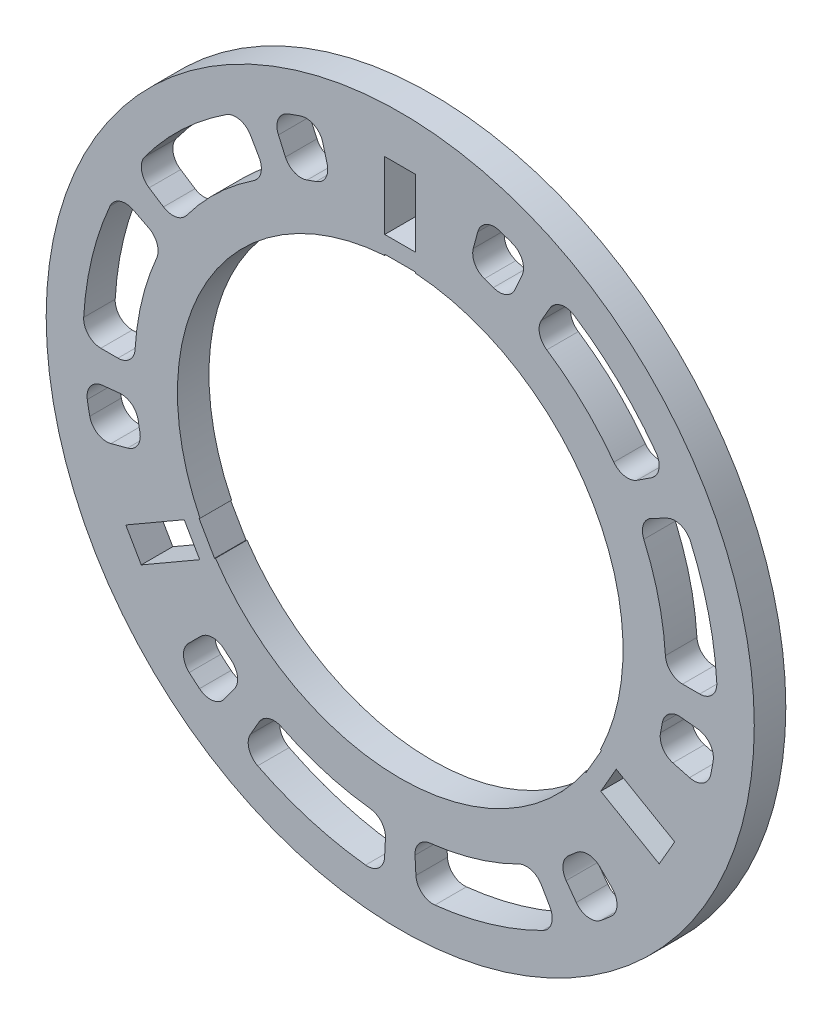
SolidWorks part; units mm, degrees
ref_plane "Front Plane" through (0, 0, 0) normal (0, 0, 1) x (1, 0, 0)
ref_plane "Top Plane" through (0, 0, 0) normal (0, 1, 0) x (1, 0, 0)
ref_plane "Right Plane" through (0, 0, 0) normal (1, 0, 0) x (0, 0, -1)
sketch "Sketch1" plane through (0, 0, 0) normal (0, 0, 1) x (1, 0, 0)
  line L0 (0, 0) -> (0, 50.8) construction
  line L1 (47.9712, -31.0114) -> (50.8422, -26.0386)
  line L2 (2.871, 57.05) -> (-2.871, 57.05)
  line L3 (2.871, 57.05) -> (2.871, 44.55)
  line L4 (2.871, 44.55) -> (-2.871, 44.55)
  line L5 (-2.871, 57.05) -> (-2.871, 44.55)
  line L6 (2.871, 57.05) -> (-2.871, 44.55) construction
  line L7 (2.871, 44.55) -> (-2.871, 57.05) construction
  line L8 (47.9712, -31.0114) -> (37.1459, -24.7614)
  line L9 (37.1459, -24.7614) -> (40.0169, -19.7886)
  line L10 (50.8422, -26.0386) -> (40.0169, -19.7886)
  line L11 (47.9712, -31.0114) -> (40.0169, -19.7886) construction
  line L12 (37.1459, -24.7614) -> (50.8422, -26.0386) construction
  line L13 (-50.8422, -26.0386) -> (-47.9712, -31.0114)
  line L14 (-50.8422, -26.0386) -> (-40.0169, -19.7886)
  line L15 (-40.0169, -19.7886) -> (-37.1459, -24.7614)
  line L16 (-47.9712, -31.0114) -> (-37.1459, -24.7614)
  line L17 (-50.8422, -26.0386) -> (-37.1459, -24.7614) construction
  line L18 (-40.0169, -19.7886) -> (-47.9712, -31.0114) construction
  line L19 (-2.871, 41.375) -> (2.871, 41.375)
  line L20 (-2.871, 41.175) -> (-2.871, 41.375)
  line L21 (2.871, 41.175) -> (2.871, 41.375)
  line L22 (34.2231, -23.0739) -> (34.3963, -23.1739)
  line L23 (37.2673, -18.2011) -> (34.3963, -23.1739)
  line L24 (37.0941, -18.1012) -> (37.2673, -18.2011)
  line L25 (-37.0941, -18.1012) -> (-37.2673, -18.2011)
  line L26 (-34.3963, -23.1739) -> (-37.2673, -18.2011)
  line L27 (0, 0) -> (32.5438, 56.3674) construction
  line L28 (-34.2231, -23.0739) -> (-34.3963, -23.1739)
  arc A0 (-2.871, 41.175) -> (-37.0941, -18.1012) centre (0, 0) ccw
  circle A1 centre (0, 0) radius 65.0875
  circle A2 centre (0, 0) radius 50.8 construction
  arc A3 (37.0941, -18.1012) -> (2.871, 41.175) centre (0, 0) ccw
  arc A4 (-34.2231, -23.0739) -> (34.2231, -23.0739) centre (0, 0) ccw
  point P21 (0, 0)
  point P32 (0, 0)
  point P34 (0, 0)
  dimension "D1" = 82.55
  dimension "D2" = 130.175
  dimension "D8" = 3.175
  dimension "D10" = 101.6
  dimension "D3" = 50.8
  dimension "D4" = 12.5
  dimension "D5" = 5.742
  dimension "D7" = 30
  dimension "D6" = 3
  dimension "D9" = 3
extrude "Boss-Extrude1" add sketch "Sketch1" along normal blind 5.842
sketch "Sketch3" plane through (0, 0, 5.842) normal (0, 0, 1) x (1, 0, 0)
  line L0 (0, 0) -> (0, 65.0875) construction
  line L1 (0, 0) -> (-56.3674, 32.5437) construction
  line L2 (-24.6063, 42.6193) -> (-29.3688, 50.8682)
  line L3 (-49.2125, 0) -> (-58.7375, 0)
  line L4 (-41.2731, 26.803) -> (-49.2614, 31.9907)
  line L5 (-43.8487, 22.342) -> (-52.3355, 26.6663)
  line L6 (43.8487, 22.342) -> (52.3355, 26.6663)
  line L7 (41.2731, 26.803) -> (49.2614, 31.9907)
  line L8 (24.6063, 42.6193) -> (29.3688, 50.8682)
  line L9 (49.2125, 0) -> (58.7375, 0)
  line L10 (-2.5756, -49.1451) -> (-3.0741, -58.657)
  line L11 (2.5756, -49.1451) -> (3.0741, -58.657)
  line L12 (24.6062, -42.6193) -> (29.3687, -50.8682)
  line L13 (-24.6063, -42.6193) -> (-29.3688, -50.8682)
  line L14 (-20.0165, 44.9579) -> (-23.8907, 53.6594)
  line L15 (-15.2024, 56.7361) -> (-12.7371, 47.5356)
  line L16 (-56.7361, -15.2024) -> (-47.5356, -12.7371)
  line L17 (-48.9429, -5.1441) -> (-58.4157, -6.1397)
  line L18 (48.9429, -5.1441) -> (58.4157, -6.1397)
  line L19 (56.7361, -15.2024) -> (47.5356, -12.7371)
  line L20 (15.2024, 56.7361) -> (12.7371, 47.5356)
  line L21 (20.0165, 44.9579) -> (23.8907, 53.6594)
  line L22 (-28.9264, -39.8137) -> (-34.525, -47.5196)
  line L23 (-41.5337, -41.5337) -> (-34.7985, -34.7985)
  line L24 (41.5337, -41.5337) -> (34.7985, -34.7985)
  line L25 (28.9264, -39.8137) -> (34.525, -47.5196)
  circle A0 centre (0, 0) radius 65.0875 construction
  arc A1 (-29.3688, 50.8682) -> (-49.2614, 31.9907) centre (0, 0) ccw
  arc A2 (-24.6063, 42.6193) -> (-41.2731, 26.803) centre (0, 0) ccw
  arc A3 (-43.8487, 22.342) -> (-49.2125, 0) centre (0, 0) ccw
  circle A4 centre (0, 0) radius 49.2125 construction
  circle A5 centre (0, 0) radius 58.7375 construction
  arc A6 (-52.3355, 26.6663) -> (-58.7375, 0) centre (0, 0) ccw
  arc A7 (58.7375, 0) -> (52.3355, 26.6663) centre (0, 0) ccw
  arc A8 (49.2614, 31.9907) -> (29.3688, 50.8682) centre (0, 0) ccw
  arc A9 (41.2731, 26.803) -> (24.6063, 42.6193) centre (0, 0) ccw
  arc A10 (49.2125, 0) -> (43.8487, 22.342) centre (0, 0) ccw
  arc A11 (-29.3688, -50.8682) -> (-3.0741, -58.657) centre (0, 0) ccw
  arc A12 (3.0741, -58.657) -> (29.3687, -50.8682) centre (0, 0) ccw
  arc A13 (2.5756, -49.1451) -> (24.6062, -42.6193) centre (0, 0) ccw
  arc A14 (-24.6063, -42.6193) -> (-2.5756, -49.1451) centre (0, 0) ccw
  arc A15 (-24.6063, 42.6193) -> (-41.2731, 26.803) centre (0, 0) ccw
  arc A16 (-29.3688, 50.8682) -> (-49.2614, 31.9907) centre (0, 0) ccw
  arc A17 (-43.8487, 22.342) -> (-49.2125, 0) centre (0, 0) ccw
  arc A18 (-52.3355, 26.6663) -> (-58.7375, 0) centre (0, 0) ccw
  arc A19 (-24.6063, -42.6193) -> (-2.5756, -49.1451) centre (0, 0) ccw
  arc A20 (-29.3688, -50.8682) -> (-3.0741, -58.657) centre (0, 0) ccw
  arc A21 (2.5756, -49.1451) -> (24.6062, -42.6193) centre (0, 0) ccw
  arc A22 (3.0741, -58.657) -> (29.3687, -50.8682) centre (0, 0) ccw
  arc A23 (58.7375, 0) -> (52.3355, 26.6663) centre (0, 0) ccw
  arc A24 (49.2125, 0) -> (43.8487, 22.342) centre (0, 0) ccw
  arc A25 (41.2731, 26.803) -> (24.6063, 42.6193) centre (0, 0) ccw
  arc A26 (49.2614, 31.9907) -> (29.3688, 50.8682) centre (0, 0) ccw
  arc A27 (-12.7371, 47.5356) -> (-20.0165, 44.9579) centre (0, 0) ccw
  arc A28 (-15.2024, 56.7361) -> (-23.8907, 53.6594) centre (0, 0) ccw
  arc A29 (-56.7361, -15.2024) -> (-58.4157, -6.1397) centre (0, 0) cw
  arc A30 (-47.5356, -12.7371) -> (-48.9429, -5.1441) centre (0, 0) cw
  arc A31 (56.7361, -15.2024) -> (58.4157, -6.1397) centre (0, 0) ccw
  arc A32 (47.5356, -12.7371) -> (48.9429, -5.1441) centre (0, 0) ccw
  arc A33 (15.2024, 56.7361) -> (23.8907, 53.6594) centre (0, 0) cw
  arc A34 (12.7371, 47.5356) -> (20.0165, 44.9579) centre (0, 0) cw
  arc A35 (-41.5337, -41.5337) -> (-34.525, -47.5196) centre (0, 0) ccw
  arc A36 (-34.7985, -34.7985) -> (-28.9264, -39.8137) centre (0, 0) ccw
  arc A37 (41.5337, -41.5337) -> (34.525, -47.5196) centre (0, 0) cw
  arc A38 (34.7985, -34.7985) -> (28.9264, -39.8137) centre (0, 0) cw
  point P8 (56.171, 17.1732)
  point P13 (49.2125, 0)
  point P38 (0, 0)
  point P63 (0, 0)
  dimension "D2" = 117.475
  dimension "D1" = 60
  dimension "D4" = 30
  dimension "D5" = 3
  dimension "D7" = 36
  dimension "D8" = 45
  dimension "D3" = 9.525
  dimension "D6" = 3
  dimension "D9" = 3
extrude "Cut-Extrude2" cut sketch "Sketch3" against normal through all contours A2 L2 A1 L4 | L5 A6 L3 A3 | L16 A30 L17 A29 | L15 A28 L14 A27 | L20 A34 L21 A33 | A9 L7 A8 L8 | A10 L9 A7 L6 | A32 L19 A31 L18 | L24 A38 L25 A37 | A13 L11 A12 L12 | A14 L13 A11 L10 | A36 L23 A35 L22 region at (-36.9066, 38.8915, 5.842) region at (-52.1343, 12.5163, 5.842) region at (52.1343, 12.5163, 5.842) region at (36.9066, 38.8915, 5.842) region at (-15.2277, -51.4078, 5.842) region at (15.2277, -51.4078, 5.842) region at (-18.0454, 50.9587, 5.842) region at (-53.1542, -9.8516, 5.842) region at (53.1542, -9.8516, 5.842) region at (18.0454, 50.9587, 5.842) region at (-35.1088, -41.1071, 5.842) region at (35.1088, -41.1071, 5.842)
fillet "Fillet1" radius 3.175 48 edges at (-52.3355, 26.6663, 2.921) (-58.4157, -6.1397, 2.921) (-43.8487, 22.342, 2.921) (-48.9429, -5.1441, 2.921) (-58.7375, 0, 2.921) (-56.7361, -15.2024, 2.921) (-47.5356, -12.7371, 2.921) (-49.2125, 0, 2.921) (-41.2731, 26.803, 2.921) (-49.2614, 31.9907, 2.921) (-20.0165, 44.9579, 2.921) (-12.7371, 47.5356, 2.921) (-15.2024, 56.7361, 2.921) (-23.8907, 53.6594, 2.921) (-29.3688, 50.8682, 2.921) (-24.6063, 42.6193, 2.921) (41.5337, -41.5337, 2.921) (34.525, -47.5196, 2.921) (34.7985, -34.7985, 2.921) (28.9264, -39.8137, 2.921) (3.0741, -58.657, 2.921) (2.5756, -49.1451, 2.921) (24.6062, -42.6193, 2.921) (29.3687, -50.8682, 2.921) (-3.0741, -58.657, 2.921) (-2.5756, -49.1451, 2.921) (-29.3688, -50.8682, 2.921) (-24.6063, -42.6193, 2.921) (-28.9264, -39.8137, 2.921) (-41.5337, -41.5337, 2.921) (-34.7985, -34.7985, 2.921) (-34.525, -47.5196, 2.921) (48.9429, -5.1441, 2.921) (58.4157, -6.1397, 2.921) (56.7361, -15.2024, 2.921) (47.5356, -12.7371, 2.921) (58.7375, 0, 2.921) (49.2125, 0, 2.921) (52.3355, 26.6663, 2.921) (43.8487, 22.342, 2.921) (49.2614, 31.9907, 2.921) (41.2731, 26.803, 2.921) (29.3688, 50.8682, 2.921) (23.8907, 53.6594, 2.921) (15.2024, 56.7361, 2.921) (24.6063, 42.6193, 2.921) (12.7371, 47.5356, 2.921) (20.0165, 44.9579, 2.921)
sketch "Sketch4" plane through (0, 0, 5.842) normal (0, 0, 1) x (1, 0, 0)
  circle A0 centre (0, 0) radius 65.0875
  circle A1 centre (0, 0) radius 65.5875
  point P3 (0, 0)
  dimension "D1" = 0.5
extrude "Boss-Extrude2" add sketch "Sketch4" against normal up to surface (5.842 mm away) up to face at (-15.0326, -50.7493, 0)
sketch "Sketch5" plane through (0, 0, 5.842) normal (0, 0, 1) x (1, 0, 0)
  line L0 (0, 0) -> (64.6093, 37.3022) construction
  line L1 (0, 0) -> (0, 44.55) construction
  line L2 (-2.871, 44.55) -> (2.871, 44.55) construction
  circle A0 centre (46.7437, 26.9875) radius 3.175
  circle A1 centre (46.7437, 26.9875) radius 6.35
  dimension "D2" = 6.35
  dimension "D4" = 12.7
  dimension "D1" = 60
  dimension "D3" = 53.975
